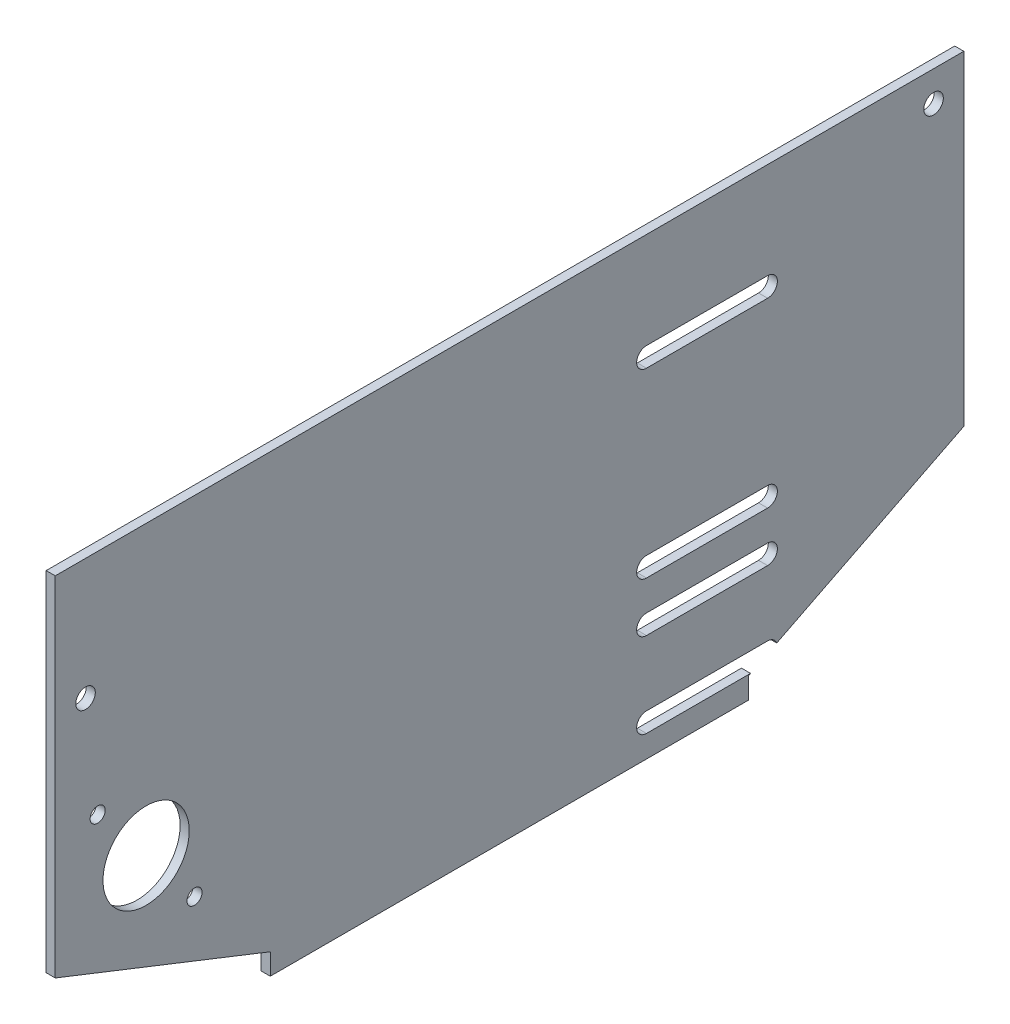
SolidWorks part; units mm, degrees
ref_plane "Front Plane" through (0, 0, 0) normal (0, 0, 1) x (1, 0, 0)
ref_plane "Top Plane" through (0, 0, 0) normal (0, 1, 0) x (1, 0, 0)
ref_plane "Right Plane" through (0, 0, 0) normal (1, 0, 0) x (0, 0, -1)
sketch "Sketch1" plane through (0, 0, 0) normal (1, 0, 0) x (0, 0, -1)
  line L1 (0, 0) -> (300, 0)
  line L2 (0, 0) -> (0, 150)
  line L3 (0, 150) -> (300, 150)
  line L4 (300, 0) -> (300, 150)
  circle A0 centre (30, 55) radius 14.235
  dimension "D1" = 300
  dimension "D5" = 28.47
  dimension "D4" = 55
  dimension "D2" = 150
  dimension "D3" = 30
extrude "Boss-Extrude1" add sketch "Sketch1" along normal blind 3
sketch "Sketch2" plane through (0, 0, 0) normal (-1, 0, 0) x (0, 0, 1)
  line L0 (-235.202, 55) -> (-195.202, 55) construction
  line L1 (-235.202, 58.225) -> (-195.202, 58.225)
  line L2 (-235.202, 51.775) -> (-195.202, 51.775)
  line L3 (-195.202, 115) -> (-235.202, 115) construction
  line L4 (-195.202, 111.77) -> (-235.202, 111.77)
  line L5 (-195.202, 118.23) -> (-235.202, 118.23)
  line L6 (-235.202, 38.55) -> (-195.202, 38.55) construction
  line L9 (-235.202, 41.775) -> (-195.202, 41.775)
  line L10 (-235.202, 35.325) -> (-195.202, 35.325)
  line L11 (-235.202, 10.55) -> (-195.202, 10.55) construction
  line L12 (-235.202, 13.775) -> (-195.202, 13.775)
  line L13 (-235.202, 7.325) -> (-195.202, 7.325)
  line L14 (0, 0) -> (-300, 0) construction
  line L15 (-300, 150) -> (0, 150) construction
  line L16 (-300, 0) -> (-300, 150) construction
  line L17 (0, 150) -> (0, 0) construction
  arc A0 (-235.202, 58.225) -> (-235.202, 51.775) centre (-235.202, 55) ccw
  arc A1 (-195.202, 51.775) -> (-195.202, 58.225) centre (-195.202, 55) ccw
  arc A3 (-195.202, 111.77) -> (-195.202, 118.23) centre (-195.202, 115) ccw
  arc A4 (-235.202, 118.23) -> (-235.202, 111.77) centre (-235.202, 115) ccw
  arc A7 (-235.202, 41.775) -> (-235.202, 35.325) centre (-235.202, 38.55) ccw
  arc A8 (-195.202, 35.325) -> (-195.202, 41.775) centre (-195.202, 38.55) ccw
  arc A9 (-235.202, 13.775) -> (-235.202, 7.325) centre (-235.202, 10.55) ccw
  arc A10 (-195.202, 7.325) -> (-195.202, 13.775) centre (-195.202, 10.55) ccw
  circle A11 centre (-290, 140) radius 3.225
  circle A12 centre (-10, 110) radius 3.225
  circle A13 centre (-290, 30) radius 3.225
  point P2 (-215.202, 55)
  point P9 (-215.202, 115)
  point P22 (-215.202, 38.55)
  point P34 (-215.202, 10.55)
  dimension "D1" = 3.225
  dimension "D4" = 3.225
  dimension "D6" = 40
  dimension "D8" = 3.225
  dimension "D13" = 6.45
  dimension "D14" = 6.45
  dimension "D15" = 6.45
  dimension "D3" = 40
  dimension "D5" = 40
  dimension "D7" = 10
  dimension "D9" = 40
  dimension "D10" = 60
  dimension "D11" = 28
  dimension "D12" = 55
  dimension "D16" = 10
  dimension "D17" = 10
  dimension "D18" = 30
  dimension "D19" = 10
  dimension "D20" = 10
  dimension "D21" = 110
extrude "Cut-Extrude1" cut sketch "Sketch2" against normal up to next
sketch "Sketch3" plane through (3, 0, 0) normal (1, 0, 0) x (0, 0, -1)
  line L0 (0, 150) -> (0, 0) construction
  line L1 (0, 0) -> (300, 0) construction
  circle A1 centre (14.0057, 74.7318) radius 2.4892
  circle A2 centre (45.9943, 35.2682) radius 2.4892
  dimension "D1" = 14.0057
  dimension "D2" = 45.9943
  dimension "D3" = 74.7318
  dimension "D4" = 35.2682
extrude "Cut-Extrude2" cut sketch "Sketch3" against normal through all
sketch "Sketch4" plane through (3, 0, 0) normal (1, 0, 0) x (0, 0, -1)
  line L0 (71, 7) -> (0, 35)
  line L1 (0, 150) -> (0, 0) construction
  line L2 (0, 35) -> (0, 0)
  line L3 (0, 0) -> (71, 0)
  line L4 (0, 0) -> (300, 0) construction
  line L5 (71, 7) -> (71, 0) construction
  line L6 (71, 0) -> (71, 7)
  dimension "D1" = 35
  dimension "D2" = 71
  dimension "D3" = 7
extrude "Cut-Extrude3" cut sketch "Sketch4" against normal through all
sketch "Sketch5" plane through (3, 0, 0) normal (1, 0, 0) x (0, 0, -1)
  line L0 (228.924, 7) -> (300, 42.7545)
  line L1 (300, 0) -> (300, 150) construction
  line L2 (300, 42.7545) -> (300, 0)
  line L3 (300, 0) -> (228.924, 0)
  line L4 (71, 0) -> (300, 0) construction
  line L5 (228.924, 7) -> (228.924, 0) construction
  line L6 (228.924, 0) -> (228.924, 7)
extrude "Cut-Extrude4" cut sketch "Sketch5" against normal blind 10
